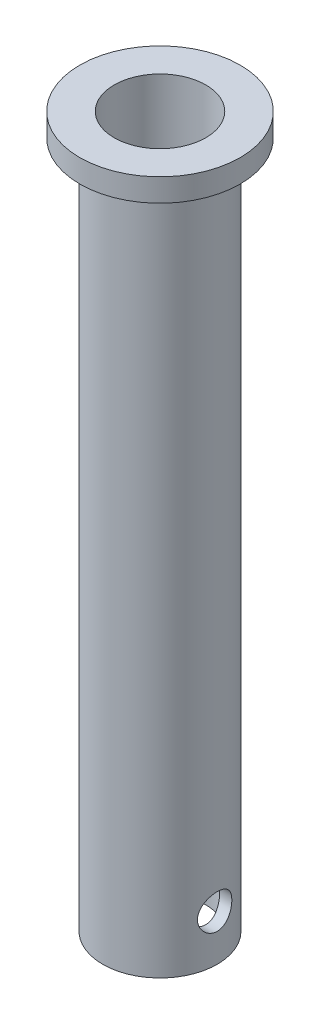
SolidWorks part; units mm, degrees
ref_plane "Front Plane" through (0, 0, 0) normal (0, 0, 1) x (1, 0, 0)
ref_plane "Top Plane" through (0, 0, 0) normal (0, 1, 0) x (1, 0, 0)
ref_plane "Right Plane" through (0, 0, 0) normal (1, 0, 0) x (0, 0, -1)
sketch "Sketch1" plane through (0, 0, 0) normal (0, 1, 0) x (1, 0, 0)
  circle A0 centre (0, 0) radius 25
  circle A1 centre (0, 0) radius 20
  circle A2 centre (0, 0) radius 35
  dimension "D1" = 50
  dimension "D2" = 40
  dimension "D3" = 70
extrude "Boss-Extrude1" add sketch "Sketch1" along normal blind 10 contours A0 A1 | A2 A0 region at (-24.2929, 0, 0) region at (-34.0101, 0, 0)
extrude "Boss-Extrude4" add sketch "Sketch1<6>" against normal blind 300 contours A0 A1 region at (-24.2929, 0, 0)
sketch "Sketch1<6>" plane through (0, 0, 0) normal (0, 1, 0) x (1, 0, 0) same geometry as "Sketch1"
sketch "Sketch2" plane through (0, 0, 0) normal (1, 0, 0) x (0, 0, -1)
  line L0 (0, -300) -> (0, 0) construction
  line L1 (-25, -300) -> (25, -300) construction
  circle A0 centre (0, -280) radius 7.5
  dimension "D1" = 15
  dimension "D2" = 20
extrude "Cut-Extrude2" cut sketch "Sketch2" against normal through all and the other way through all contours A0
